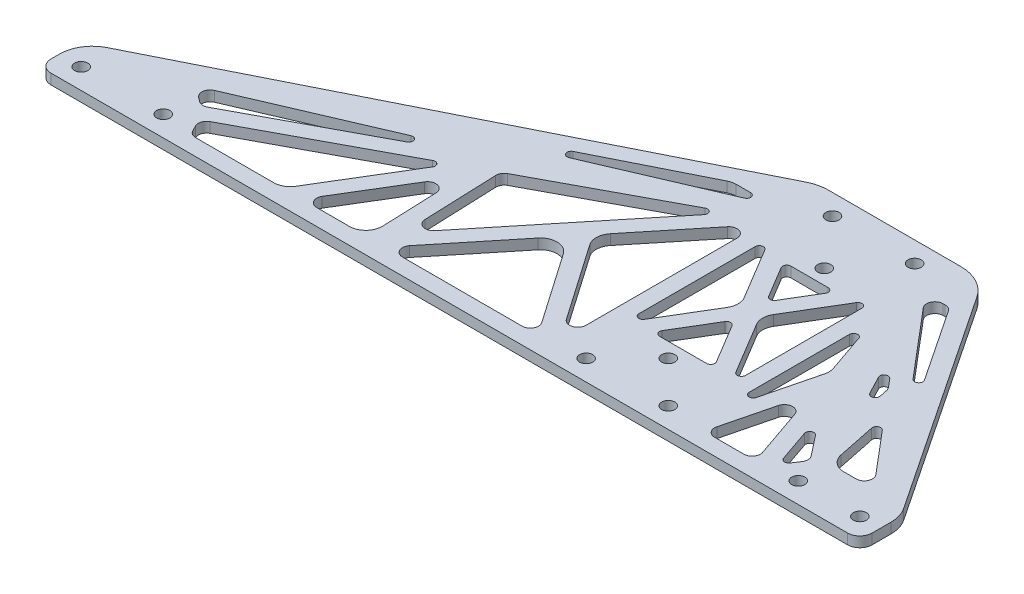
SolidWorks part; units mm, degrees
ref_plane "Front Plane" through (0, 0, 0) normal (0, 0, 1) x (1, 0, 0)
ref_plane "Top Plane" through (0, 0, 0) normal (0, 1, 0) x (1, 0, 0)
ref_plane "Right Plane" through (0, 0, 0) normal (1, 0, 0) x (0, 0, -1)
sketch "Sketch1" plane through (0, 0, 0) normal (0, 1, 0) x (1, 0, 0)
  line L0 (0, 0) -> (254, 0)
  line L2 (203.2, 88.9) -> (152.4, 88.9)
  line L4 (0, 0) -> (0, 12.7)
  line L5 (0, 12.7) -> (152.4, 88.9)
  line L6 (203.2, 88.9) -> (254, 12.7)
  line L7 (254, 12.7) -> (254, 0)
  line L8 (0, 6.35) -> (41.2306, 6.35) construction
  line L9 (254, 6.35) -> (220.1675, 6.35) construction
  line L10 (139.7, 82.55) -> (207.4333, 82.55) construction
  line L11 (156.6333, 76.2) -> (38.0113, 12.7) construction
  line L12 (38.0113, 12.7) -> (22.7185, 24.0592)
  line L13 (226.5259, 15.8112) -> (251.9259, 15.8112)
  line L20 (127, 76.2) -> (211.6667, 76.2)
  line L21 (226.5259, 15.8112) -> (215.9, 0)
  line L22 (38.0113, 12.7) -> (44.45, 0)
  line L23 (156.6333, 76.2) -> (27.2885, 20.6647) construction
  line L24 (156.6333, 76.2) -> (98.8302, 5.08) construction
  line L28 (194.7333, 76.2) -> (226.5259, 15.8112) construction
  line L31 (5.08, 9.5604) -> (153.5992, 83.82)
  line L32 (200.4813, 83.82) -> (153.5992, 83.82)
  line L33 (200.4813, 83.82) -> (248.92, 11.1619)
  line L34 (248.92, 11.1619) -> (248.92, 5.08)
  line L35 (5.08, 5.08) -> (248.92, 5.08)
  line L36 (5.08, 5.08) -> (5.08, 9.5604)
  line L37 (219.314, 5.08) -> (194.7333, 76.2) construction
  line L39 (194.7333, 76.2) -> (245.8205, 15.8112) construction
  line L40 (98.8302, 5.08) -> (97.3223, 44.45) construction
  line L41 (127.7318, 40.64) -> (152.3892, 5.08) construction
  line L42 (207.0237, 40.64) -> (198.1092, 5.08) construction
  line L83 (226.5259, 15.8112) -> (220.2769, 46.0056) construction
  line L84 (207.0237, 40.64) -> (226.5259, 15.8112) construction
  line L107 (97.3223, 44.45) -> (73.4302, 5.08) construction
  line L108 (156.6333, 76.2) -> (194.7333, 12.7) construction
  line L113 (194.7333, 76.2) -> (156.6333, 12.7) construction
  line L114 (155.6312, 78.534) -> (26.2864, 22.9986)
  line L115 (155.4346, 78.4393) -> (36.8125, 14.9393)
  line L116 (154.6622, 77.802) -> (101.1104, 11.9127)
  line L117 (156.6333, 12.7) -> (154.0933, 8.1397)
  line L118 (156.6333, 12.7) -> (194.7333, 12.7)
  line L119 (194.7333, 12.7) -> (200.3598, 0)
  line L120 (153.0965, 6.35) -> (197.5465, 6.35) construction
  line L123 (101.1104, 11.9127) -> (99.5369, 52.9951)
  line L124 (99.5369, 52.9951) -> (96.1931, 47.4852)
  line L125 (125.6445, 39.1927) -> (150.3019, 3.6327)
  line L126 (192.5553, 77.5068) -> (154.4553, 14.0068)
  line L127 (154.4553, 74.8932) -> (192.5553, 11.3932)
  line L128 (156.6333, 12.7) -> (156.6333, 76.2) construction
  line L129 (194.7333, 12.7) -> (194.7333, 76.2) construction
  line L130 (197.2733, 12.7) -> (197.2733, 76.2)
  line L131 (159.1733, 12.7) -> (159.1733, 76.2)
  line L132 (192.1933, 12.7) -> (192.1933, 76.2)
  line L133 (154.0933, 12.7) -> (154.0933, 76.2)
  line L134 (205.8201, 46.2844) -> (228.5234, 17.3801)
  line L137 (205.8201, 46.2844) -> (195.6454, 5.6976)
  line L138 (221.7147, 5.9097) -> (197.134, 77.0297)
  line L139 (192.4858, 75.0167) -> (224.2783, 14.6279)
  line L140 (229.0132, 16.3259) -> (222.7642, 46.5203)
  line L141 (157.6354, 73.866) -> (28.2906, 18.3307)
  line L142 (157.8321, 73.9607) -> (39.21, 10.4607)
  line L143 (158.6044, 74.598) -> (96.5501, -1.7527)
  line L144 (96.5501, -1.7527) -> (95.1077, 35.9049)
  line L145 (95.1077, 35.9049) -> (75.6017, 3.7622)
  line L146 (129.8191, 42.0873) -> (154.4765, 6.5273)
  line L147 (196.9114, 74.8932) -> (158.8114, 11.3932)
  line L148 (158.8114, 77.5068) -> (196.9114, 14.0068)
  line L149 (208.2273, 34.9956) -> (224.5284, 14.2422)
  line L150 (208.2273, 34.9956) -> (200.5729, 4.4624)
  line L151 (216.9134, 4.2503) -> (192.3327, 75.3703)
  line L152 (196.9809, 77.3833) -> (228.7734, 16.9944)
  line L153 (224.0386, 15.2964) -> (217.7896, 45.4908)
  line L154 (71.2588, 6.3978) -> (70.4591, 5.08)
  line L155 (36.8125, 14.9393) -> (35.7571, 14.3744)
  line L156 (39.21, 10.4607) -> (39.1601, 10.434)
  line L157 (154.0933, 12.7) -> (154.0933, 7.0799)
  line L158 (197.2733, 12.7) -> (197.2733, 6.9667)
  line L159 (224.5284, 14.2422) -> (225.0366, 13.5952)
  line L160 (229.0132, 16.3259) -> (229.1197, 15.8112)
  line L161 (192.7942, 74.5595) -> (243.8813, 14.1707)
  line L162 (196.6725, 77.8405) -> (247.7597, 17.4517)
  line L163 (153.766, 7.552) -> (149.5598, 0)
  line L164 (95.5112, 46.3615) -> (71.2588, 6.3978)
  line L165 (99.5369, 52.9951) -> (71.2588, 6.3978) construction
  line L166 (175.6833, 19.05) -> (162.9833, 6.35) construction
  line L167 (175.6833, 19.05) -> (188.3833, 6.35) construction
  line L168 (162.9833, 82.55) -> (175.6833, 67.31) construction
  line L169 (175.6833, 67.31) -> (188.3833, 82.55) construction
  line L170 (161.6625, 21.082) -> (189.7041, 21.082) construction
  line L171 (161.6625, 23.622) -> (189.7041, 23.622)
  line L172 (163.1865, 65.278) -> (188.1801, 65.278) construction
  line L173 (163.1865, 62.738) -> (188.1801, 62.738)
  circle A0 centre (6.7733, 6.35) radius 2.032
  circle A1 centre (32.1733, 6.35) radius 2.032
  circle A2 centre (228.6, 6.35) radius 2.032
  circle A3 centre (247.65, 6.35) radius 2.032
  circle A4 centre (162.9833, 82.55) radius 2.032
  circle A5 centre (188.3833, 82.55) radius 2.032
  circle A28 centre (162.9833, 6.35) radius 2.032
  circle A29 centre (188.3833, 6.35) radius 2.032
  arc A32 (197.2733, 12.7) -> (192.1933, 12.7) centre (194.7333, 12.7) cw
  arc A33 (197.2733, 76.2) -> (192.1933, 76.2) centre (194.7333, 76.2) ccw
  arc A34 (159.1733, 12.7) -> (154.0933, 12.7) centre (156.6333, 12.7) cw
  arc A35 (159.1733, 76.2) -> (154.0933, 76.2) centre (156.6333, 76.2) ccw
  arc A37 (155.6312, 78.534) -> (157.6354, 73.866) centre (156.6333, 76.2) cw
  arc A38 (26.2864, 22.9986) -> (28.2906, 18.3307) centre (27.2885, 20.6647) ccw
  arc A39 (155.4346, 78.4393) -> (157.8321, 73.9607) centre (156.6333, 76.2) cw
  arc A40 (36.8125, 14.9393) -> (39.21, 10.4607) centre (38.0113, 12.7) ccw
  arc A41 (154.6622, 77.802) -> (158.6044, 74.598) centre (156.6333, 76.2) cw
  arc A42 (71.2588, 6.3978) -> (75.6017, 3.7622) centre (73.4302, 5.08) ccw
  arc A43 (125.6445, 39.1927) -> (129.8191, 42.0873) centre (127.7318, 40.64) cw
  arc A44 (150.3019, 3.6327) -> (154.4765, 6.5273) centre (152.3892, 5.08) ccw
  arc A45 (192.5553, 77.5068) -> (196.9114, 74.8932) centre (194.7333, 76.2) cw
  arc A46 (154.4553, 14.0068) -> (158.8114, 11.3932) centre (156.6333, 12.7) ccw
  arc A47 (154.4553, 74.8932) -> (158.8114, 77.5068) centre (156.6333, 76.2) cw
  arc A48 (192.5553, 11.3932) -> (196.9114, 14.0068) centre (194.7333, 12.7) ccw
  arc A49 (228.5234, 17.3801) -> (224.5284, 14.2422) centre (226.5259, 15.8112) cw
  arc A50 (195.6454, 5.6976) -> (200.5729, 4.4624) centre (198.1092, 5.08) ccw
  arc A51 (221.7147, 5.9097) -> (216.9134, 4.2503) centre (219.314, 5.08) cw
  arc A52 (197.134, 77.0297) -> (192.3327, 75.3703) centre (194.7333, 76.2) ccw
  arc A53 (192.4858, 75.0167) -> (196.9809, 77.3833) centre (194.7333, 76.2) cw
  arc A54 (224.2783, 14.6279) -> (228.7734, 16.9944) centre (226.5259, 15.8112) ccw
  arc A55 (229.0132, 16.3259) -> (224.0386, 15.2964) centre (226.5259, 15.8112) cw
  arc A56 (222.7642, 46.5203) -> (217.7896, 45.4908) centre (220.2769, 46.0056) ccw
  arc A57 (192.7942, 74.5595) -> (196.6725, 77.8405) centre (194.7333, 76.2) cw
  arc A58 (243.8813, 14.1707) -> (247.7597, 17.4517) centre (245.8205, 15.8112) ccw
  circle A59 centre (175.6833, 19.05) radius 2.032
  circle A60 centre (175.6833, 67.31) radius 2.032
  dimension "D7" = 4.064
  dimension "D8" = 25.4
  dimension "D9" = 130.81
  dimension "D10" = 19.05
  dimension "D11" = 6.35
  dimension "D13" = 19.05
  dimension "D1" = 254
  dimension "D2" = 50.8
  dimension "D3" = 88.9
  dimension "D4" = 152.4
  dimension "D5" = 12.7
  dimension "D6" = 6.35
  dimension "D12" = 25.4
  dimension "D14" = 44.45
  dimension "D15" = 19.05
  dimension "D16" = 25.4
  dimension "D18" = 12.7
  dimension "D19" = 38.1
  dimension "D20" = 19.05
  dimension "D21" = 12.7
  dimension "D22" = 25.4
  dimension "D23" = 50.8
  dimension "D24" = 25.4
  dimension "D29" = 6.35
  dimension "D30" = 38.1
  dimension "D31" = 25.4
  dimension "D32" = 6.35
  dimension "D33" = 2.54
  dimension "D34" = 50.8
  dimension "D35" = 7.552
  dimension "D36" = 12.7
  dimension "D38" = 15.24
  dimension "D39" = 2.54
  dimension "D40" = 2.54
  dimension "D17" = 5.08
  dimension "D25" = 2.54
  dimension "D26" = 2.54
  dimension "D27" = 2.54
  dimension "D28" = 2.54
  dimension "D37" = 2.54
extrude "Boss-Extrude1" add sketch "Sketch1" along normal blind 3.175 contours L0 L7 L6 L2 L5 L4 | A0 | A1 | A5 | A4 | A2 | A3
extrude "Cut-Extrude2" cut sketch "Sketch1<3>" along normal through all contours L142 L156 L22 L35 L154 L124 | L155 L115 L124 L141 L12 | L144 L145 L35 | L116 L142 L123 | L125 L143 L35 | L157 L133 L143 L146 L117 | L114 L20 L31 | L130 L158 L137 L151 | L35 L151 L150 | L161 L152 L153 | L161 L140 L160 L13 | L159 L149 L138 L21 | L20 L162 L33 | L131 L126 L127 | L147 L148 L132 | L115 L141 L123 | L147 L171 L127 | L173 L148 L126 | A28 | A29 | A59 | A60 region at (64.7257, 0, -16.4796) region at (89.2658, 0, -15.355) region at (126.3241, 0, -15.5249) region at (118.3245, 0, -64.21) region at (56.1323, 0, -27.8913) region at (146.3644, 0, -38.8822) region at (115.9087, 0, -40.9571) region at (100.9162, 0, -49.3843) region at (212.3574, 0, -62.2554) region at (208.2553, 0, -13.9673) region at (220.1621, 0, -16.1676) region at (199.6409, 0, -37.9304) region at (163.6893, 0, -44.45) region at (175.6833, 0, -58.2876) region at (232.1338, 0, -22.7875) region at (215.3763, 0, -44.8583) region at (175.6833, 0, -28.919) region at (187.6774, 0, -44.45)
sketch "Sketch1<3>" plane through (0, 0, 0) normal (0, 1, 0) x (1, 0, 0) same geometry as "Sketch1"
fillet "Fillet1" radius 3.81 2 edges at (254, 1.5875, 0) (0, 1.5875, 0)
fillet "Fillet2" radius 10.16 2 edges at (254, 1.5875, -12.7) (0, 1.5875, -12.7)
fillet "Fillet3" radius 12.7 2 edges at (203.2, 1.5875, -88.9) (152.4, 1.5875, -88.9)
fillet "Fillet4" radius 1.27 23 edges at (214.3608, 1.5875, -27.1869) (233.4505, 1.5875, -34.3662) (207.8157, 1.5875, -56.8029) (220.3926, 1.5875, -32.9136) (197.2733, 1.5875, -61.0753) (197.2733, 1.5875, -12.1914) (159.1733, 1.5875, -67.0298) (192.1933, 1.5875, -67.0298) (192.1933, 1.5875, -21.8702) (159.1733, 1.5875, -21.8702) (146.6944, 1.5875, -67.9985) (66.4191, 1.5875, -40.2299) (150.1953, 1.5875, -76.2) (224.7883, 1.5875, -36.74) (103.3533, 1.5875, -50.5595) (90.3319, 1.5875, -37.8269) (183.694, 1.5875, -62.738) (167.6727, 1.5875, -62.738) (175.6833, 1.5875, -49.3869) (185.218, 1.5875, -23.622) (166.1487, 1.5875, -23.622) (175.6833, 1.5875, -39.5131) (221.0887, 1.5875, -7.7208)
fillet "Fillet5" radius 2.54 20 edges at (39.1601, 1.5875, -10.434) (41.8745, 1.5875, -5.08) (99.9212, 1.5875, -42.9602) (101.1104, 1.5875, -11.9127) (95.1077, 1.5875, -35.9049) (76.4014, 1.5875, -5.08) (35.7571, 1.5875, -14.3744) (29.6468, 1.5875, -18.913) (198.0603, 1.5875, -76.2) (205.5613, 1.5875, -76.2) (217.9205, 1.5875, -44.8583) (242.4935, 1.5875, -15.8112) (216.6266, 1.5875, -5.08) (200.7278, 1.5875, -5.08) (207.4116, 1.5875, -31.7419) (154.0933, 1.5875, -69.0476) (149.2983, 1.5875, -5.08) (102.1034, 1.5875, -5.08) (154.0933, 1.5875, -7.0799) (225.0366, 1.5875, -13.5952)
fillet "Fillet6" radius 5.08 9 edges at (229.1197, 1.5875, -15.8112) (96.2884, 1.5875, -5.08) (172.7212, 1.5875, -44.45) (178.6455, 1.5875, -44.45) (130.9066, 1.5875, -40.519) (127.5708, 1.5875, -36.4147) (138.3592, 1.5875, -76.2) (70.4591, 1.5875, -5.08) (204.3761, 1.5875, -40.5246)
